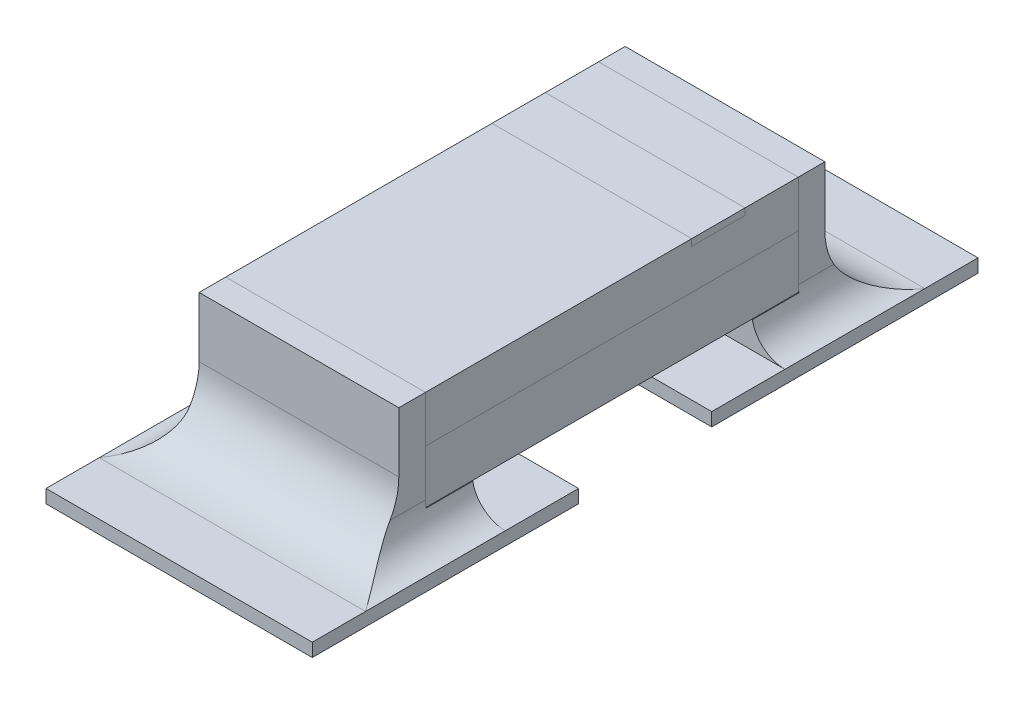
SolidWorks part; units mm, degrees
ref_plane "Front Plane" through (0, 0, 0) normal (0, 0, 1) x (1, 0, 0)
ref_plane "Top Plane" through (0, 0, 0) normal (0, 1, 0) x (1, 0, 0)
ref_plane "Right Plane" through (0, 0, 0) normal (1, 0, 0) x (0, 0, -1)
sketch "Sketch1" plane through (0, 0, 0) normal (0, 0, 1) x (1, 0, 0)
  line L1 (-0.75, 0.5) -> (0.75, 0.5)
  line L2 (-0.75, 0.5) -> (-0.75, 0.1)
  line L3 (-0.75, 0.1) -> (0.75, 0.1)
  line L4 (0.75, 0.5) -> (0.75, 0.1)
  line L5 (-0.75, 0.5) -> (0.75, 0.1) construction
  line L6 (-0.75, 0.1) -> (0.75, 0.5) construction
  point P0 (0, 0.3)
  point P5 (0, 29.1575)
  point P6 (-0.6067, 12.4033)
  point P7 (0, 0)
  point P8 (0.6745, 5.148)
  point P10 (0, 0)
  dimension "D1" = 0.4
  dimension "D2" = 1.5
  dimension "D3" = 0.3
extrude "Boss-Extrude1" add sketch "Sketch1" along normal mid plane 2.8
sketch "Sketch2" plane through (0, 0, 0) normal (1, 0, 0) x (0, 0, -1)
  line L0 (-1.6, 0.85) -> (-1.4, 0.85)
  line L1 (-1.4, 0.1) -> (-1.4, 0.5) construction
  line L2 (-1.4, 0.85) -> (-1.4, 0.1)
  line L3 (-1.4, 0.1) -> (-1.05, 0.1)
  line L4 (-1.4, 0.1) -> (1.4, 0.1) construction
  line L5 (-1.05, 0.1) -> (-1.05, -0.1)
  line L6 (-1.05, -0.1) -> (-1.6, -0.1)
  line L7 (-1.6, -0.1) -> (-1.6, 0.85)
  dimension "D1" = 0.95
  dimension "D2" = 0.2
  dimension "D3" = 0.55
extrude "Boss-Extrude2" add sketch "Sketch2" along normal mid plane 1.5 separate body
sketch "Sketch3" plane through (0, 0.5, 0) normal (0, 1, 0) x (1, 0, 0)
  line L4 (0.75, 1.4) -> (-0.75, 1.4)
  line L5 (-0.75, 1.4) -> (-0.75, -1.4)
  line L6 (-0.75, -1.4) -> (0.75, -1.4)
  line L7 (0.75, -1.4) -> (0.75, 1.4)
  line L8 (0.75, 1.4) -> (-0.75, 1.4)
  line L9 (-0.75, 1.4) -> (-0.75, -1.4)
  line L10 (-0.75, -1.4) -> (0.75, -1.4)
  line L11 (0.75, -1.4) -> (0.75, 1.4)
  dimension "D1" = 0
extrude "Boss-Extrude3" add sketch "Sketch3" along normal up to surface (0.35 mm away) separate body up to face at (0, 0.85, 1.5)
sketch "Sketch4" plane through (0, -0.1, 0) normal (0, -1, 0) x (1, 0, 0)
  line L1 (-1, 2.5) -> (1, 2.5)
  line L2 (-1, 2.5) -> (-1, 0.5)
  line L3 (-1, 0.5) -> (1, 0.5)
  line L4 (1, 2.5) -> (1, 0.5)
  line L5 (-1, 2.5) -> (1, 0.5) construction
  line L6 (-1, 0.5) -> (1, 2.5) construction
  point P0 (0, 1.5)
  point P5 (0, 0)
  point P6 (0, 1.3644)
  dimension "D1" = 2
  dimension "D2" = 0.5
extrude "Boss-Extrude4" add sketch "Sketch4" along normal blind 0.1
sketch "Sketch5" plane through (0, 0.85, 0) normal (0, 1, 0) x (1, 0, 0)
  line L0 (-0.75, -1.4) -> (-0.75, 1.4) construction
  line L1 (-0.75, 1) -> (0.75, 1)
  line L2 (-0.75, 1) -> (-0.75, 0.6)
  line L3 (-0.75, 0.6) -> (0.75, 0.6)
  line L4 (0.75, 1) -> (0.75, 0.6)
  line L5 (-0.75, 1) -> (0.75, 0.6) construction
  line L6 (-0.75, 0.6) -> (0.75, 1) construction
  point P0 (0, 0.8)
  point P7 (0, 0)
  dimension "D1" = 0.4
  dimension "D2" = 1
extrude "Cut-Extrude1" cut sketch "Sketch5" against normal blind 0.05
extrude "Boss-Extrude5" add sketch "Sketch5<2>" against normal blind 0.05 separate body
sketch "Sketch5<2>" plane through (0, 0.85, 0) normal (0, 1, 0) x (1, 0, 0) same geometry as "Sketch5"
fillet "Fillet1" radius 0.5 1 edges at (0, -0.1, 1.6)
fillet "Fillet2" radius 0.25 2 edges at (-0.75, -0.1, 1.575) (0.75, -0.1, 1.575)
mirror "Mirror1" about plane through (0, 0, 0) normal (0, 0, 1) of bodies 104
